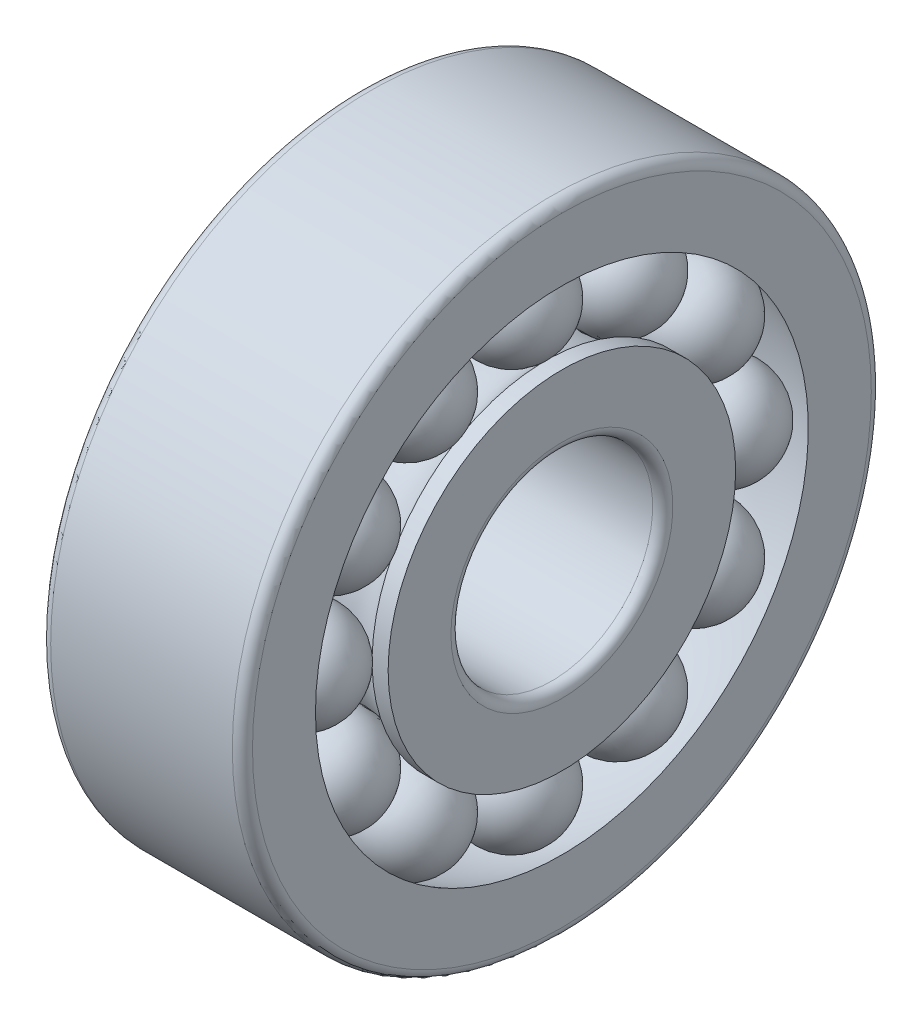
SolidWorks part; units mm, degrees
ref_plane "Front" through (0, 0, 0) normal (0, 0, 1) x (1, 0, 0)
ref_plane "Top" through (0, 0, 0) normal (0, 1, 0) x (1, 0, 0)
ref_plane "Right" through (0, 0, 0) normal (1, 0, 0) x (0, 0, -1)
sketch "Sketch1" plane through (0, 0, 0) normal (0, 0, 1) x (1, 0, 0)
  line L0 (0, 0) -> (10.4156, 0) construction
  line L1 (-3, 3) -> (3, 3)
  line L2 (3, 3) -> (3, 5.1667)
  line L3 (3, 5.1667) -> (2.523, 5.1667)
  line L4 (-3, 5.1667) -> (-3, 3)
  line L5 (-2.523, 5.1667) -> (-3, 5.1667)
  line L6 (0.477, 5.1667) -> (-0.477, 5.1667)
  circle A0 centre (-1.5, 6.25) radius 1.49 construction
  circle A1 centre (1.5, 6.25) radius 1.49 construction
  arc A2 (-2.523, 5.1667) -> (-0.477, 5.1667) centre (-1.5, 6.25) ccw
  arc A3 (0.477, 5.1667) -> (2.523, 5.1667) centre (1.5, 6.25) ccw
  point P8 (0, 3)
  dimension "D1" = 1.5
  dimension "D2" = 1.5
revolve "Revovle1" add sketch "Sketch1" angle 360 about L0
sketch "Sketch2" plane through (0, 0, 0) normal (0, 0, 1) x (1, 0, 0)
  line L0 (-2.9995, 6.25) -> (-0.0005, 6.25)
  line L1 (-4.0336, 6.25) -> (6.5093, 6.25) construction
  arc A2 (-2.9995, 6.25) -> (-0.0005, 6.25) centre (-1.5, 6.25) ccw
  dimension "D1" = 6.25
  dimension "QXD" = 2.999
  dimension "D2" = 1.5
revolve "Revolve2" add sketch "Sketch2" angle 360 about L1
mirror "Mirror1" about plane through (0, 0, 0) normal (1, 0, 0) of "Revolve2"
sketch "Sketch3" plane through (0, 0, 0) normal (0, 0, 1) x (1, 0, 0)
  line L0 (-3, 7.3271) -> (-3, 9.5)
  line L1 (-3, 9.5) -> (3, 9.5)
  line L2 (3, 9.5) -> (3, 7.3271)
  line L5 (0, 0) -> (7.3928, 0) construction
  line L7 (3, -5.1667) -> (3, 5.1667) construction
  line L8 (-3, 5.1667) -> (-3, -5.1667) construction
  circle A0 centre (-1.5, 6.25) radius 1.49 construction
  circle A1 centre (1.5, 6.25) radius 1.49 construction
  arc A2 (3, 7.3271) -> (-3, 7.3271) centre (0, 0) ccw
  dimension "D2" = 2.98
  dimension "D1" = 6.25
  dimension "D3" = 1.5
  dimension "D4" = 1.5
revolve "Revolve3" add sketch "Sketch3" angle 360 about L5
pattern_circular "Circular-Pattern1" count 12 over 360 about axis through (0, 0, 0) along (1, 0, 0) of "Revolve2", "Mirror1"
fillet "Fillet1" radius 0.3 4 edges at (-3, 0, 3) (-3, 0, 9.5) (3, 0, 3) (3, 0, 9.5)
equation "\"XD1@Sketch1\" = \"XD@Sketch1\" +  ( \"DD@Sketch3\" - \"XD@Sketch1\" )  / 3"
equation "\"QDD@Sketch1\" = \"XD@Sketch1\" +  ( \"DD@Sketch3\" - \"XD@Sketch1\" )  / 2"
equation "\"QXD@Sketch1\" = \"DB@Sketch1\" / 2 - 0.02"
equation "\"D1@Sketch1\" = \"DB@Sketch1\" / 4"
equation "\"D2@Sketch1\" = \"D1@Sketch1\""
equation "\"QXD@Sketch2\" = \"DB@Sketch1\"/2-0.001"
equation "\"D2@Sketch2\" = \"D2@Sketch1\""
equation "\"D1@Sketch2\" = \"QDD@Sketch1\" / 2"
equation "\"D1@Sketch3\" = \"QDD@Sketch1\" / 2"
equation "\"D2@Sketch3\" = \"QXD@Sketch1\""
equation "\"D3@Sketch3\" = \"D2@Sketch1\""
equation "\"D4@Sketch3\" = \"D3@Sketch3\""
equation "\"D1@Circular-Pattern1\" = int( 3.14159265 / atn(( \"QXD@Sketch2\" / 2) / sqr(\"QDD@Sketch1\" *\"QDD@Sketch1\"/4 - ( \"QXD@Sketch2\" / 2) *  ( \"QXD@Sketch2\" / 2))))"
